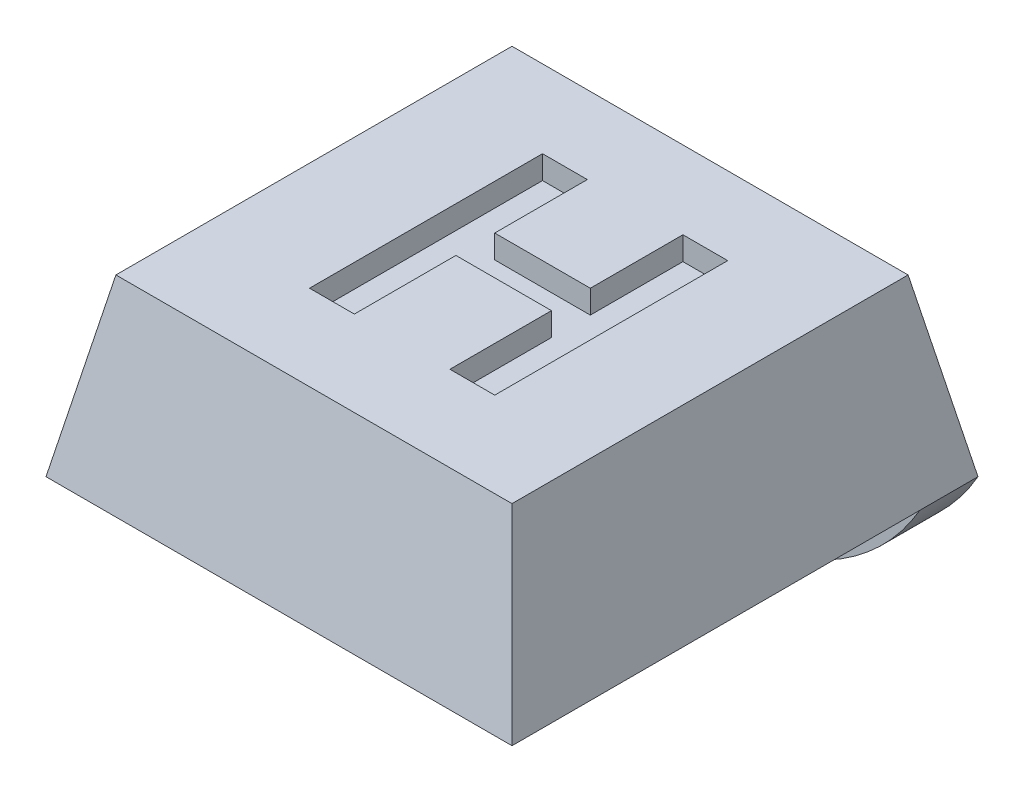
SolidWorks part; units mm, degrees
ref_plane "Front Plane" through (0, 0, 0) normal (0, 0, 1) x (1, 0, 0)
ref_plane "Top Plane" through (0, 0, 0) normal (0, 1, 0) x (1, 0, 0)
ref_plane "Right Plane" through (0, 0, 0) normal (1, 0, 0) x (0, 0, -1)
sketch "Sketch1" plane through (0, 0, 0) normal (0, 1, 0) x (1, 0, 0)
  line L1 (0, 0) -> (8, 0)
  line L2 (0, 0) -> (0, 8)
  line L3 (0, 8) -> (8, 8)
  line L4 (8, 0) -> (8, 8)
  dimension "D1" = 8
  dimension "D2" = 8
extrude "Boss-Extrude1" add sketch "Sketch1" along normal blind 3
sketch "Sketch2" plane through (0, 0, 0) normal (0, 0, 1) x (1, 0, 0)
  line L0 (0, 0) -> (0.6, 3)
  line L1 (0, 3) -> (8, 3) construction
  line L2 (0.6, 3) -> (0, 3)
  line L3 (0, 3) -> (0, 0)
  line L4 (8, 0) -> (7.4, 3)
  line L5 (7.4, 3) -> (8, 3)
  line L6 (8, 3) -> (8, 0)
  dimension "D1" = 0.6
  dimension "D2" = 0.6
extrude "Cut-Extrude1" cut sketch "Sketch2" against normal through all both and the other way through all
sketch "Sketch3" plane through (0, 0, 0) normal (1, 0, 0) x (0, 0, -1)
  line L0 (0, 0) -> (0.6, 3)
  line L1 (8, 3) -> (0, 3) construction
  line L2 (0.6, 3) -> (0, 3)
  line L3 (0, 3) -> (0, 0)
  line L4 (8, 3) -> (7.4, 3)
  line L5 (7.4, 3) -> (8, 0)
  line L6 (8, 3) -> (8, 0)
  dimension "D1" = 0.6
  dimension "D2" = 0.6
extrude "Cut-Extrude2" cut sketch "Sketch3" along normal blind 11
sketch "Sketch4" plane through (0, 0, 0) normal (0, -1, 0) x (1, 0, 0)
  line L0 (8, 0) -> (8, -8) construction
  line L3 (0, 0) -> (8, 0) construction
  circle A0 centre (4, -3.75) radius 1.8
  dimension "D1" = 3.6
  dimension "D2" = 4
  dimension "D3" = 3.75
extrude "Cut-Extrude3" cut sketch "Sketch4" against normal blind 0.8
sketch "Sketch5" plane through (0, 0, 0) normal (0, -1, 0) x (1, 0, 0)
  line L0 (8, 0) -> (8, -8) construction
  line L1 (0, -8) -> (8, -8)
  line L2 (0, -8) -> (0, -7)
  line L3 (0, -7) -> (8, -7)
  line L4 (8, -8) -> (8, -7)
  dimension "D1" = 1
extrude "Boss-Extrude2" add sketch "Sketch5" along normal blind 2
fillet "Fillet1" radius 4 2 edges at (8, -2, -7.5) (0, -2, -7.5)
sketch "Sketch6" plane through (0, 3, 0) normal (0, 1, 0) x (1, 0, 0)
  text T0 "H" font "Arial" height 4
extrude "Cut-Extrude4" cut sketch "Sketch6" against normal blind 0.4
